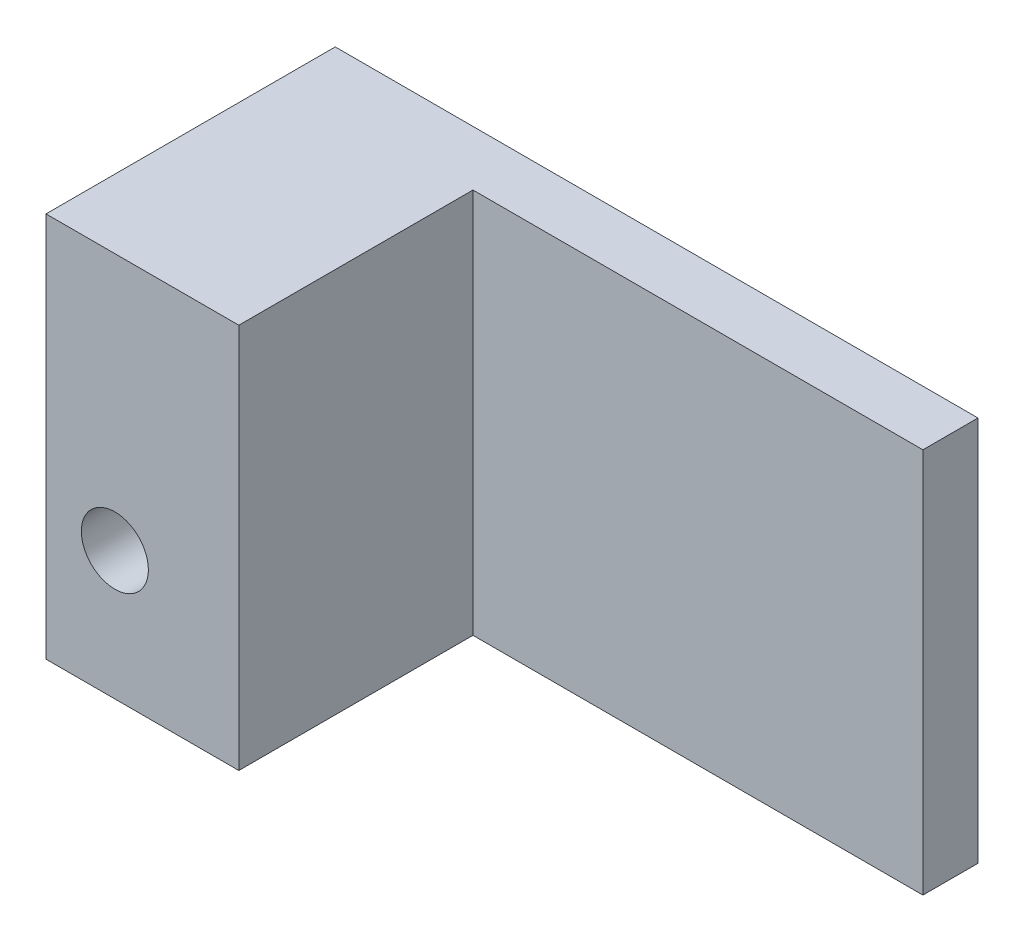
SolidWorks part; units mm, degrees
ref_plane "Front Plane" through (0, 0, 0) normal (0, 0, 1) x (1, 0, 0)
ref_plane "Top Plane" through (0, 0, 0) normal (0, 1, 0) x (1, 0, 0)
ref_plane "Right Plane" through (0, 0, 0) normal (1, 0, 0) x (0, 0, -1)
sketch "Sketch1" plane through (0, 0, 0) normal (0, 1, 0) x (1, 0, 0)
  line L0 (0, -12.75) -> (0, 12.75) construction
  line L1 (-24.5, -12.75) -> (24.5, -12.75)
  line L2 (-24.5, -12.75) -> (-24.5, 12.75)
  line L3 (-24.5, 12.75) -> (24.5, 12.75)
  line L4 (24.5, -12.75) -> (24.5, 12.75)
  line L5 (-24.5, -12.75) -> (24.5, 12.75) construction
  line L6 (-24.5, 12.75) -> (24.5, -12.75) construction
  line L7 (0, 12.75) -> (0, 15.75)
  line L9 (0, 15.75) -> (-27.5, 15.75)
  line L10 (0, 15.75) -> (0, 12.75)
  line L11 (0, 12.75) -> (-27.5, 12.75)
  line L12 (-27.5, 15.75) -> (-27.5, 12.75)
  line L13 (-24.5, 12.75) -> (-27.5, 12.75)
  line L14 (-24.5, 12.75) -> (-24.5, 0)
  line L15 (-24.5, 0) -> (-27.5, 0)
  line L16 (-27.5, 12.75) -> (-27.5, 0)
  line L17 (-27.5, 0) -> (-35, 0)
  line L18 (-27.5, 0) -> (-27.5, 3)
  line L19 (-27.5, 3) -> (-35, 3)
  line L20 (-35, 0) -> (-35, 3)
  line L21 (-35, 3) -> (-27.5, 3)
  line L22 (-35, 3) -> (-35, 15.75)
  line L23 (-35, 15.75) -> (-27.5, 15.75)
  line L24 (-27.5, 3) -> (-27.5, 15.75)
  point P0 (0, 0)
  dimension "D1" = 49
  dimension "D2" = 25.5
  dimension "D3" = 3
  dimension "D4" = 27.5
  dimension "D5" = 12.75
  dimension "D6" = 7.5
  dimension "D7" = 3
extrude "Boss-Extrude1" add sketch "Sketch1" along normal blind 21 contours L11 L3 L7 L9 L12 | L16 L15 L2 L11 | L12 L16 | L20 L17 L16 L19 region at (-26, 0, -6.375) region at (-13.75, 0, -14.25) region at (-31.25, 0, -1.5) region at (-31.25, 0, -9.375)
sketch "Sketch2" plane through (0, 0, 0) normal (0, 0, 1) x (1, 0, 0)
  line L0 (-27.5, 0) -> (-27.5, 21) construction
  line L1 (-24.5, 0) -> (-35, 0) construction
  line L2 (-24.5, 21) -> (-35, 21) construction
  line L3 (-24.5, 21) -> (-24.5, 0) construction
  line L4 (-27.5, 14) -> (-35, 14)
  line L5 (-35, 21) -> (-35, 0) construction
  line L6 (-35, 14) -> (-27.5, 0) construction
  line L7 (-27.5, 0) -> (-35, 0) construction
  line L8 (-35, 0) -> (-27.5, 14) construction
  circle A0 centre (-31.25, 7) radius 1.825
  dimension "D3" = 3.65
  dimension "D1" = 3
  dimension "D2" = 7
extrude "Cut-Extrude1" cut sketch "Sketch2" against normal blind 3 contours A0 region at (-31.25, 7, 0)
